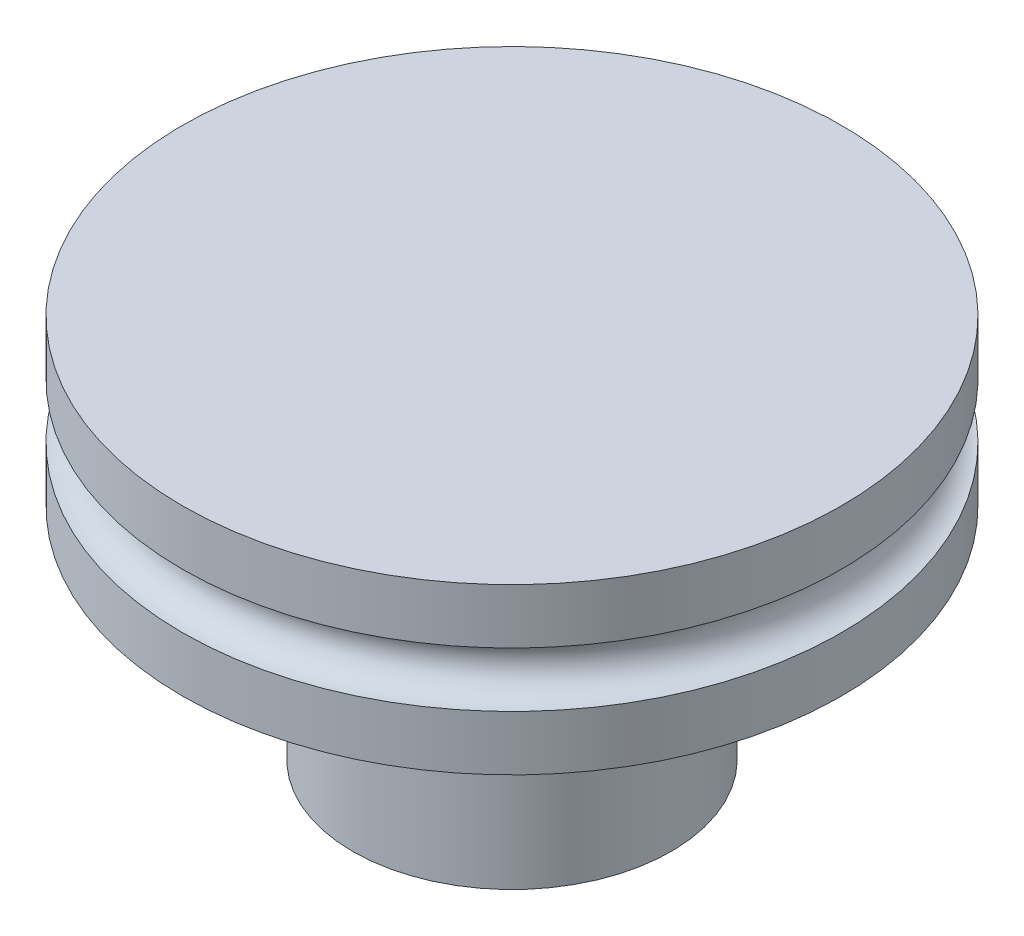
SolidWorks part; units mm, degrees
ref_plane "Front Plane" through (0, 0, 0) normal (0, 0, 1) x (1, 0, 0)
ref_plane "Top Plane" through (0, 0, 0) normal (0, 1, 0) x (1, 0, 0)
ref_plane "Right Plane" through (0, 0, 0) normal (1, 0, 0) x (0, 0, -1)
sketch "Sketch1" plane through (0, 0, 0) normal (0, 1, 0) x (1, 0, 0)
  circle A0 centre (0, 0) radius 2.9
  dimension "D1" = 5.8
extrude "Boss-Extrude1" add sketch "Sketch1" along normal blind 3
sketch "Sketch4" plane through (0, 3, 0) normal (0, 1, 0) x (1, 0, 0)
  circle A0 centre (0, 0) radius 3.6
  dimension "D1" = 7.2
extrude "Boss-Extrude3" add sketch "Sketch4" along normal blind 1
sketch "Sketch2" plane through (0, 4, 0) normal (0, 1, 0) x (1, 0, 0)
  circle A0 centre (0, 0) radius 6
  dimension "D1" = 12
extrude "Boss-Extrude2" add sketch "Sketch2" along normal blind 3
ref_axis "Axis1" through (0, 9.1152, 0) along (0, -1, 0)
sketch "Sketch3" plane through (0, 0, 0) normal (0, 0, 1) x (1, 0, 0)
  line L0 (-6, 7) -> (-6, 4) construction
  circle A0 centre (-6, 5.5) radius 0.5
  dimension "D1" = 1
revolve "Cut-Revolve1" cut sketch "Sketch3" angle 360 about axis through (0, 9.1152, 0) along (0, -1, 0)
